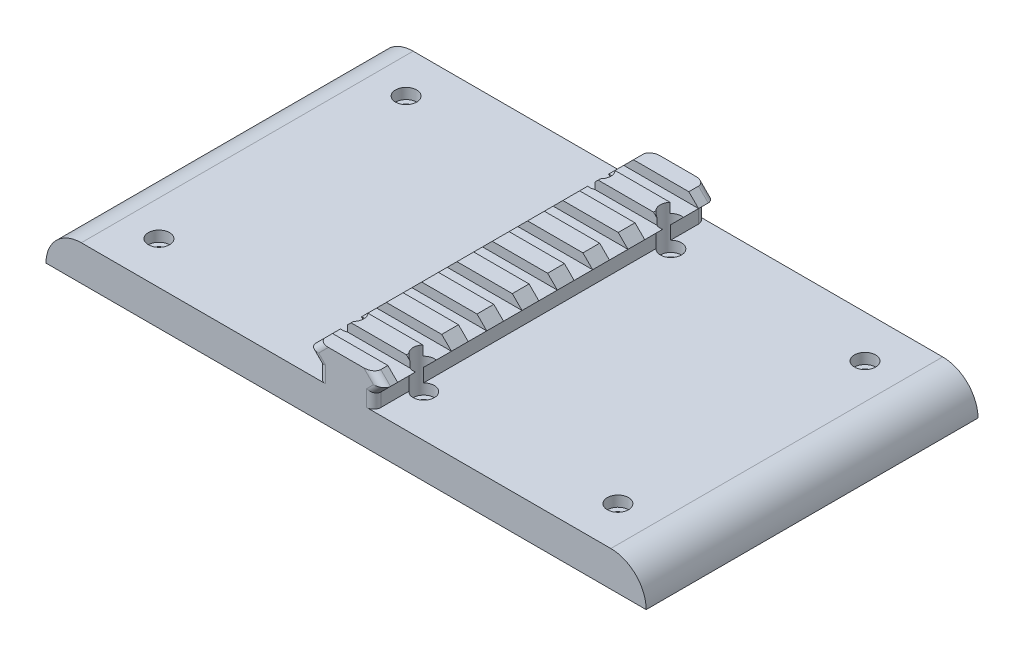
SolidWorks part; units mm, degrees
material "ABS"
ref_plane "前视基准面" through (0, 0, 0) normal (0, 0, 1) x (1, 0, 0)
ref_plane "上视基准面" through (0, 0, 0) normal (0, 1, 0) x (1, 0, 0)
ref_plane "右视基准面" through (0, 0, 0) normal (1, 0, 0) x (0, 0, -1)
sketch "草图2" plane through (0, 0, 0) normal (0, 0, 1) x (1, 0, 0)
  line L0 (7.84, 9.32) -> (10.6, 6.56)
  line L1 (7.84, 9.32) -> (-7.84, 9.32)
  line L2 (-7.84, 9.32) -> (-10.6, 6.56)
  line L3 (-10.6, 6.56) -> (-7.84, 3.8)
  line L4 (-7.84, 3.8) -> (-7.84, 0)
  line L5 (-7.84, 0) -> (7.84, 0)
  line L6 (10.6, 6.56) -> (7.84, 3.8)
  line L7 (7.84, 3.8) -> (7.84, 0)
  dimension "D1" = 3.8
  dimension "D2" = 5.52
  dimension "D3" = 21.2
  dimension "D4" = 90
sketch "草图3" plane through (0, 0, 0) normal (0, 0, 1) x (1, 0, 0)
  line L0 (-7.84, 0) -> (7.84, 0) construction
  line L1 (-75, 0) -> (75, 0)
  line L3 (-75, -10) -> (75, -10)
  line L5 (-85, -10) -> (-75, -10)
  line L6 (-85, -10) -> (-75, -10)
  line L7 (0, 0) -> (0, -10) construction
  line L8 (85, -10) -> (75, -10)
  line L9 (85, -10) -> (75, -10)
  line L10 (-75, -10) -> (75, -10)
  arc A0 (-75, 0) -> (-85, -10) centre (-75, -10) ccw
  arc A1 (75, 0) -> (85, -10) centre (75, -10) cw
  point P9 (0, 0)
  point P16 (0, -10)
  dimension "D1" = 75
  dimension "D2" = 10
extrude "凸台-拉伸1" add sketch "草图3" along normal blind 94 contours L7 L1 A0 L5 L3 | L1 L7 L10 L8 A1 region at (-41.4571, -5.0717, 0) region at (41.4571, -5.0717, 0)
extrude "凸台-拉伸2" add sketch "草图2" along normal through all
sketch "草图4" plane through (0, 0, 0) normal (0, 1, 0) x (1, 0, 0)
  line L0 (0, -47) -> (44.5473, -47) construction
  line L1 (0, 0) -> (0, -45.4367) construction
  line L2 (-75, -94) -> (-75, 0) construction
  circle A0 centre (-65, -12) radius 1.5
  circle A1 centre (-10, -12) radius 1.5
  circle A2 centre (10, -12) radius 1.5
  circle A3 centre (65, -12) radius 1.5
  circle A4 centre (65, -82) radius 1.5
  circle A5 centre (10, -82) radius 1.5
  circle A6 centre (-65, -82) radius 1.5
  circle A7 centre (-10, -82) radius 1.5
  point P12 (-75, -47)
  dimension "D1" = 3
  dimension "D2" = 55
  dimension "D3" = 10
  dimension "D4" = 35
extrude "切除-拉伸1" cut sketch "草图4" against normal through all
sketch "草图5" plane through (0, 0, 0) normal (0, 1, 0) x (1, 0, 0)
  line L0 (0, 0) -> (0, 18.7044) construction
  line L1 (-117.8018, -47) -> (-101.1049, -47) construction
  line L2 (-75, -94) -> (-75, 0) construction
  circle A0 centre (-65, -12) radius 3
  circle A3 centre (-10, -12) radius 3
  circle A4 centre (10, -12) radius 3
  circle A5 centre (65, -12) radius 3
  circle A6 centre (65, -82) radius 3
  circle A7 centre (10, -82) radius 3
  circle A8 centre (-10, -82) radius 3
  circle A9 centre (-65, -82) radius 3
  point P14 (-75, -47)
  dimension "D1" = 6
extrude "切除-拉伸2" cut sketch "草图5" along normal through all from offset 3 offset against normal yes
sketch "草图6" plane through (0, 9.32, 0) normal (0, 1, 0) x (1, 0, 0)
  line L0 (-10.6, -9.0606) -> (-10.6, 0) construction
  line L1 (-10.6, -4.75) -> (10.6, -4.75)
  line L2 (-10.6, -4.75) -> (-10.6, -10)
  line L3 (-10.6, -10) -> (10.6, -10)
  line L4 (10.6, -4.75) -> (10.6, -10)
  line L5 (10.6, -9.0606) -> (10.6, 0) construction
  line L6 (7.84, 0) -> (-7.84, 0) construction
  dimension "D1" = 5.25
  dimension "D2" = 4.75
extrude "切除-拉伸3" cut sketch "草图6" against normal blind 2.76
pattern_linear "阵列(线性)1" count 9 spacing 10 along (0, 0, 1) of "切除-拉伸3"
fillet "圆角2" radius 2 12 edges at (9.22, 7.94, 94) (9.22, 5.18, 94) (-9.22, 5.18, 94) (-9.22, 7.94, 94) (9.22, 7.94, 0) (9.22, 5.18, 0) (-9.22, 5.18, 0) (-9.22, 7.94, 0) (-7.84, 1.9, 0) (7.84, 1.9, 0) (7.84, 1.9, 94) (-7.84, 1.9, 94)
